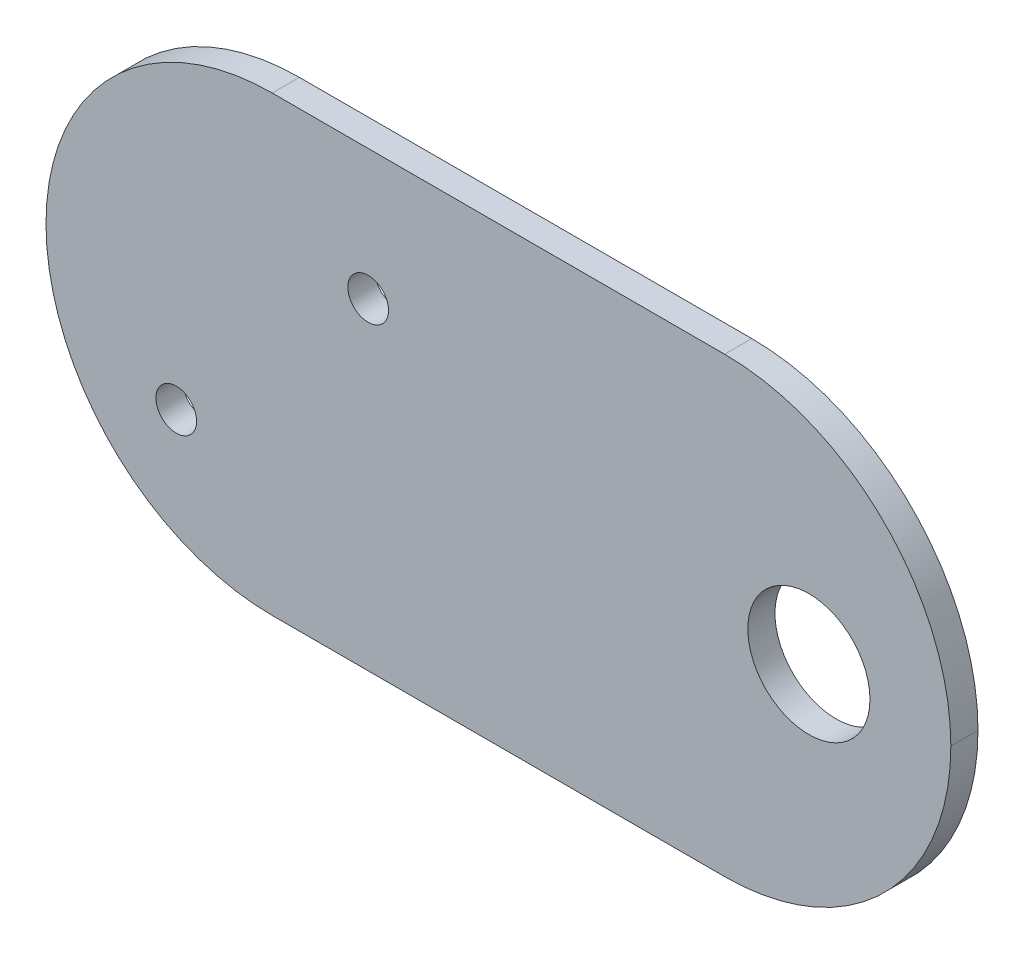
SolidWorks part; units mm, degrees
ref_plane "Front Plane" through (0, 0, 0) normal (0, 0, 1) x (1, 0, 0)
ref_plane "Top Plane" through (0, 0, 0) normal (0, 1, 0) x (1, 0, 0)
ref_plane "Right Plane" through (0, 0, 0) normal (1, 0, 0) x (0, 0, -1)
sketch "Sketch1" plane through (0, 0, 0) normal (0, 0, 1) x (1, 0, 0)
  line L1 (-50, -25) -> (50, -25)
  line L2 (-50, -25) -> (-50, 25)
  line L3 (-50, 25) -> (50, 25)
  line L4 (50, -25) -> (50, 25)
  line L5 (-50, -25) -> (50, 25) construction
  line L6 (-50, 25) -> (50, -25) construction
  point P0 (0, 0)
  dimension "D1" = 100
  dimension "D2" = 50
extrude "Boss-Extrude1" add sketch "Sketch1" along normal blind 3
sketch "Sketch2" plane through (0, 0, 3) normal (0, 0, 1) x (1, 0, 0)
  circle A0 centre (34.3105, 0) radius 6.75
  circle A1 centre (-14.3934, 10.6066) radius 2.25 construction
  circle A2 centre (-14.3934, 10.6066) radius 2.25
  circle A3 centre (-35.6066, -10.6066) radius 2.25 construction
  circle A4 centre (-35.6066, -10.6066) radius 2.25
  dimension "D1" = 13.5
extrude "Cut-Extrude1" cut sketch "Sketch2" against normal through all
fillet "Fillet1" radius 25 4 edges at (-50, -25, 1.5) (-50, 25, 1.5) (50, 25, 1.5) (50, -25, 1.5)
